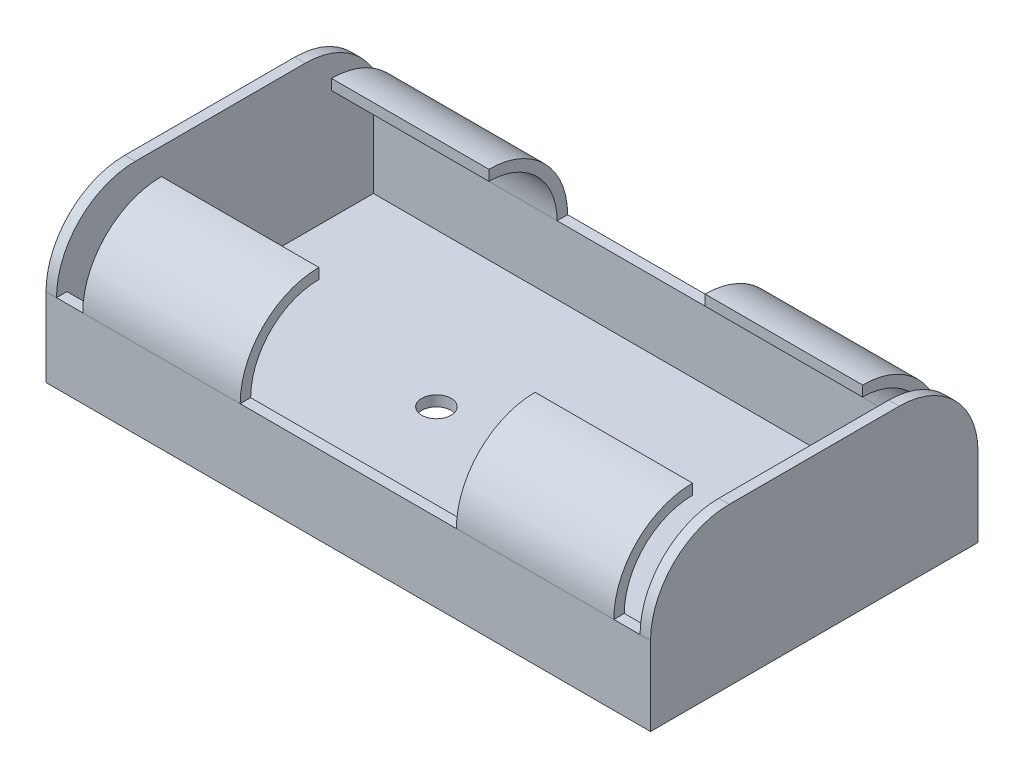
SolidWorks part; units mm, degrees
ref_plane "Front Plane" through (0, 0, 0) normal (0, 0, 1) x (1, 0, 0)
ref_plane "Top Plane" through (0, 0, 0) normal (0, 1, 0) x (1, 0, 0)
ref_plane "Right Plane" through (0, 0, 0) normal (1, 0, 0) x (0, 0, -1)
sketch "Sketch1" plane through (0, 0, 0) normal (0, 1, 0) x (1, 0, 0)
  line L1 (-28.8, 15.6) -> (28.8, 15.6)
  line L2 (-28.8, 15.6) -> (-28.8, -15.6)
  line L3 (-28.8, -15.6) -> (28.8, -15.6)
  line L4 (28.8, 15.6) -> (28.8, -15.6)
  line L5 (-28.8, 15.6) -> (28.8, -15.6) construction
  line L6 (-28.8, -15.6) -> (28.8, 15.6) construction
  point P0 (0, 0)
  dimension "D1" = 57.6
  dimension "D2" = 31.2
extrude "Boss-Extrude1" add sketch "Sketch1" along normal blind 15
fillet "Fillet1" radius 7.5 2 edges at (0, 15, -15.6) (0, 15, 15.6)
shell "Shell1" thickness 1 removed face at (0, 15, 0)
sketch "Sketch4" plane through (0, 0, 15.6) normal (0, 0, 1) x (1, 0, 0)
  line L0 (28.8, 7.5) -> (-28.8, 7.5) construction
  line L1 (-27.8, 15) -> (-25.3, 15)
  line L2 (-27.8, 15) -> (-27.8, 7.5)
  line L3 (-27.8, 7.5) -> (-25.3, 7.5)
  line L4 (-25.3, 15) -> (-25.3, 7.5)
  line L5 (-27.8, 15) -> (27.8, 15) construction
  line L6 (-10.3, 15) -> (10.3, 15)
  line L7 (-10.3, 15) -> (-10.3, 7.5)
  line L8 (-10.3, 7.5) -> (10.3, 7.5)
  line L10 (0, 0) -> (0, 7.5) construction
  line L11 (-28.8, 0) -> (28.8, 0) construction
  line L12 (10.3, 15) -> (10.3, 7.5)
  line L13 (25.3, 15) -> (25.3, 7.5)
  line L14 (27.8, 7.5) -> (25.3, 7.5)
  line L15 (27.8, 15) -> (27.8, 7.5)
  line L16 (27.8, 15) -> (25.3, 15)
  point P8 (0, 7.5)
  dimension "D1" = 2.5
  dimension "D2" = 15
extrude "Cut-Extrude1" cut sketch "Sketch4" against normal through all
sketch "Sketch5" plane through (0, 1, 0) normal (0, 1, 0) x (1, 0, 0)
  circle A0 centre (0, 0) radius 1.4
  circle A1 centre (7.2, 0) radius 1.4
  circle A2 centre (-7.2, 0) radius 1.4
  dimension "D1" = 2.8
  dimension "D2" = 7.2
  dimension "D3" = 7.2
extrude "Cut-Extrude2" cut sketch "Sketch5" against normal blind 15
